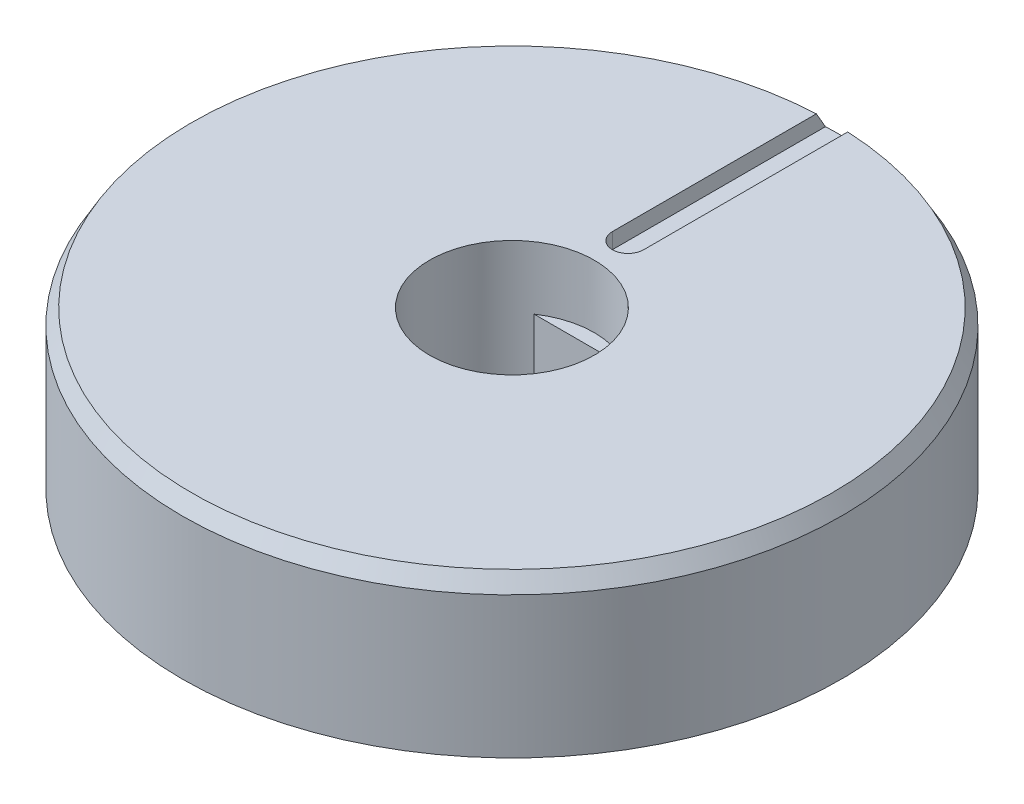
SolidWorks part; units mm, degrees
ref_plane "Front Plane" through (0, 0, 0) normal (0, 0, 1) x (1, 0, 0)
ref_plane "Top Plane" through (0, 0, 0) normal (0, 1, 0) x (1, 0, 0)
ref_plane "Right Plane" through (0, 0, 0) normal (1, 0, 0) x (0, 0, -1)
sketch "Sketch1" plane through (0, 0, 0) normal (0, 1, 0) x (1, 0, 0)
  circle A0 centre (0, 0) radius 8.6
  circle A1 centre (0, 0) radius 10.5
  dimension "D1" = 17.2
  dimension "D2" = 21
extrude "Boss-Extrude1" add sketch "Sketch1" against normal blind 4
ref_plane "Plane1" through (0, 0, 8.6) normal (0, 0, -1) x (-1, 0, 0)
sketch "Sketch2" plane through (0, 0, 8.6) normal (0, 0, -1) x (-1, 0, 0)
  line L0 (0.4, -3.75) -> (-0.4, -3.75)
  line L1 (0.4, -3.75) -> (0.4, -1.9)
  line L2 (0.4, -1.9) -> (2.3, 0)
  line L3 (10.5, 0) -> (-10.5, 0) construction
  line L4 (2.3, 0) -> (-2.3, 0)
  line L5 (-2.3, 0) -> (-0.4, -1.9)
  line L6 (-0.4, -1.9) -> (-0.4, -3.75)
  point P2 (0, -3.75)
  dimension "D1" = 3.75
  dimension "D2" = 135
  dimension "D3" = 135
  dimension "D4" = 0.8
  dimension "D5" = 1.9
extrude "Boss-Extrude2" add sketch "Sketch2" along normal blind 1.25
ref_plane "Plane2" through (0, 0, -8.6) normal (0, 0, 1) x (1, 0, 0)
extrude "Boss-Extrude3" add sketch "Sketch2<2>" against normal blind 1.25 from surface starting at plane "Plane2"
sketch "Sketch2<2>" plane through (0, 0, 8.6) normal (0, 0, -1) x (-1, 0, 0) same geometry as "Sketch2"
sketch "Sketch3" plane through (0, 0, 0) normal (0, 1, 0) x (1, 0, 0)
  circle A1 centre (0, 0) radius 10.5
  circle A2 centre (0, 0) radius 10.5
  dimension "D1" = 0
extrude "Boss-Extrude4" add sketch "Sketch3" along normal blind 1
sketch "Sketch5" plane through (0, 0, 0) normal (0, -1, 0) x (1, 0, 0)
  circle A1 centre (0, 0) radius 3.125
  dimension "D2" = 6.25
extrude "Boss-Extrude5" add sketch "Sketch5" along normal blind 9
fillet "Fillet2" radius 0.75 1 edges at (0, 0, 3.125)
sketch "Sketch4" plane through (0, 1, 0) normal (0, 1, 0) x (1, 0, 0)
  line L0 (-1.4697, 2.175) -> (1.4697, 2.175)
  line L1 (-3.1755, -2.625) -> (3.3726, -2.625) construction
  arc A0 (-1.4697, 2.175) -> (1.4697, 2.175) centre (0, 0) ccw
  dimension "D1" = 5.25
  dimension "D2" = 4.8
extrude "Cut-Extrude1" cut sketch "Sketch4" against normal blind 5.25
fillet "Fillet1" radius 0.25 4 edges at (-0.4, -3.75, 7.9703) (0.4, -3.75, 7.9703) (-0.4, -3.75, -7.9703) (0.4, -3.75, -7.9703)
sketch "Sketch7" plane through (0, 1, 0) normal (0, 1, 0) x (1, 0, 0)
  circle A2 centre (0, 0) radius 2.625
  arc A3 (-1.4697, 2.175) -> (1.4697, 2.175) centre (0, 0) ccw construction
extrude "Cut-Extrude2" cut sketch "Sketch7" against normal blind 2
sketch "Sketch9" plane through (0, 1, 0) normal (0, 1, 0) x (1, 0, 0)
  line L0 (0, 3.7) -> (0, 13.7) construction
  line L1 (-0.5, 3.7) -> (-0.5, 13.7)
  line L2 (0.5, 3.7) -> (0.5, 13.7)
  arc A0 (-0.5, 3.7) -> (0.5, 3.7) centre (0, 3.7) ccw
  arc A1 (0.5, 13.7) -> (-0.5, 13.7) centre (0, 13.7) ccw
  point P3 (0, 8.7)
  dimension "D1" = 1
  dimension "D2" = 10
  dimension "D3" = 3.7
extrude "Cut-Extrude3" cut sketch "Sketch9" against normal blind 0.5
sketch "Sketch10" plane through (0, -9, 0) normal (0, -1, 0) x (1, 0, 0)
  line L1 (1.8042, 0) -> (0.9021, 1.5625)
  line L2 (0.9021, 1.5625) -> (-0.9021, 1.5625)
  line L3 (-0.9021, 1.5625) -> (-1.8042, 0)
  line L4 (-1.8042, 0) -> (-0.9021, -1.5625)
  line L5 (-0.9021, -1.5625) -> (0.9021, -1.5625)
  line L6 (0.9021, -1.5625) -> (1.8042, 0)
  circle A0 centre (0, 0) radius 1.5625 construction
  dimension "D1" = 3.125
extrude "Cut-Extrude4" cut sketch "Sketch10" against normal blind 4
chamfer "Chamfer2" distance 0.25 angle 45 6 edges at (1.3532, -9, 0.7813) (1.3532, -9, -0.7813) (0, -9, -1.5625) (-1.3532, -9, -0.7813) (-1.3532, -9, 0.7813) (0, -9, 1.5625)
chamfer "Chamfer3" distance 0.5 angle 30 1 edges at (0, 1, 10.5) first distance on face at (0, 0.75, -5.244)
